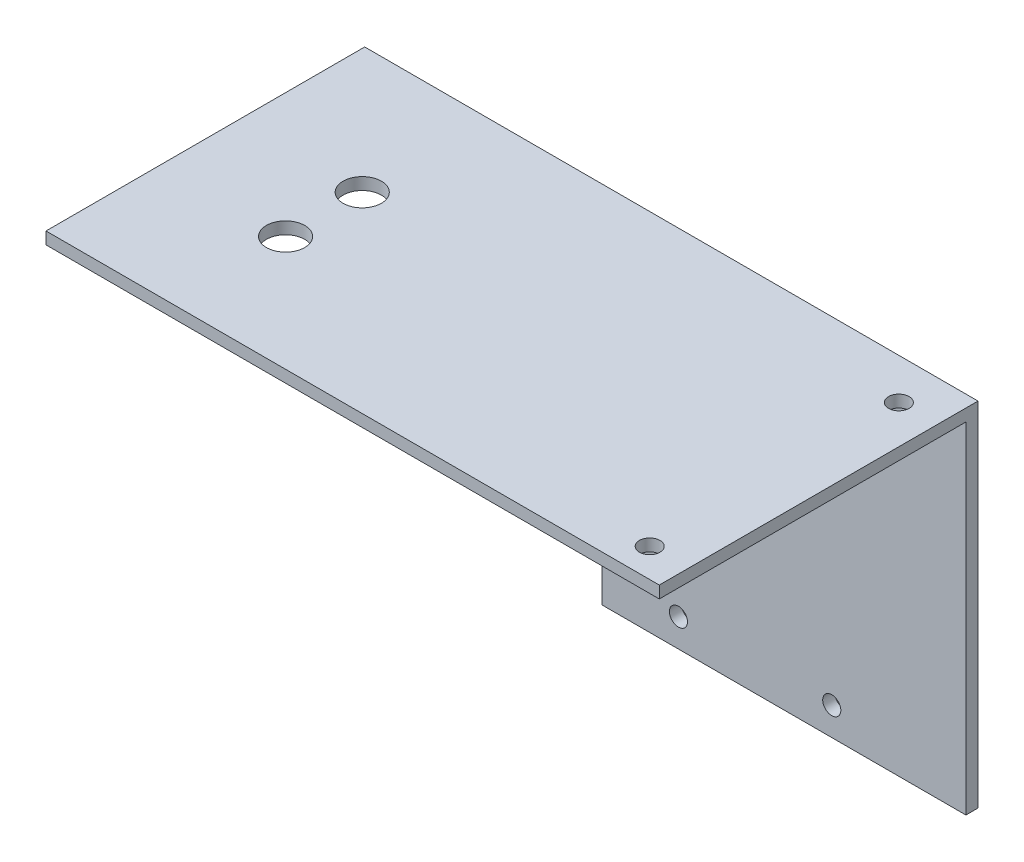
SolidWorks part; units mm, degrees
ref_plane "Front Plane" through (0, 0, 0) normal (0, 0, 1) x (1, 0, 0)
ref_plane "Top Plane" through (0, 0, 0) normal (0, 1, 0) x (1, 0, 0)
ref_plane "Right Plane" through (0, 0, 0) normal (1, 0, 0) x (0, 0, -1)
sketch "Sketch1" plane through (0, 0, 0) normal (0, 0, 1) x (1, 0, 0)
  line L0 (38.1, 51.75) -> (12.7, 51.75) construction
  line L1 (0, 58.4) -> (60.325, 58.4)
  line L2 (0, 58.4) -> (0, 0)
  line L3 (0, 0) -> (60.325, 0)
  line L4 (60.325, 58.4) -> (60.325, 0)
  line L6 (12.7, 51.75) -> (12.7, 4.65) construction
  line L8 (12.7, 4.65) -> (38.1, 4.65) construction
  line L9 (38.1, 51.75) -> (38.1, 4.65) construction
  circle A4 centre (12.7, 51.75) radius 1.5
  circle A5 centre (38.1, 51.75) radius 1.5
  circle A6 centre (12.7, 4.65) radius 1.5
  circle A7 centre (38.1, 4.65) radius 1.5
  dimension "D3" = 3
  dimension "D1" = 58.4
  dimension "D2" = 60.325
  dimension "D4" = 47.1
  dimension "D6" = 4.65
  dimension "D7" = 25.4
  dimension "D9" = 12.7
extrude "Boss-Extrude1" add sketch "Sketch1" against normal blind 2
sketch "Sketch2" plane through (0, 0, -2) normal (0, 0, -1) x (-1, 0, 0)
  line L0 (0, 56.4) -> (41.275, 56.4)
  line L1 (0, 58.4) -> (0, 0) construction
  line L2 (0, 56.4) -> (-60.325, 56.4)
  line L3 (-60.325, 56.4) -> (-60.325, 58.4)
  line L4 (-60.325, 58.4) -> (0, 58.4) construction
  line L5 (-60.325, 58.4) -> (0, 58.4)
  line L6 (41.275, 56.4) -> (41.275, 58.4)
  line L7 (41.275, 58.4) -> (0, 58.4)
  dimension "D1" = 60.325
  dimension "D2" = 41.275
  dimension "D3" = 2
extrude "Boss-Extrude2" add sketch "Sketch2" against normal blind 52.8
sketch "Sketch3" plane through (0, 58.4, 0) normal (0, 1, 0) x (1, 0, 0)
  line L0 (53.975, -4.7625) -> (53.975, -46.0375) construction
  line L1 (-20.6375, -19.05) -> (-20.6375, -31.75) construction
  line L2 (60.325, -50.8) -> (60.325, 2) construction
  line L3 (-41.275, -50.8) -> (60.325, -50.8) construction
  line L4 (-41.275, -50.8) -> (60.325, -50.8) construction
  line L5 (-41.275, -50.8) -> (-41.275, 2) construction
  circle A0 centre (53.975, -4.7625) radius 1.7
  circle A1 centre (53.975, -46.0375) radius 1.7
  circle A2 centre (-20.6375, -31.75) radius 3.175
  circle A3 centre (-20.6375, -19.05) radius 3.175
  dimension "D1" = 3.4
  dimension "D2" = 41.275
  dimension "D5" = 6.35
  dimension "D6" = 6.35
  dimension "D3" = 4.7625
  dimension "D4" = 6.35
  dimension "D7" = 12.7
  dimension "D8" = 19.05
  dimension "D9" = 20.6375
extrude "Cut-Extrude1" cut sketch "Sketch3" against normal through all
